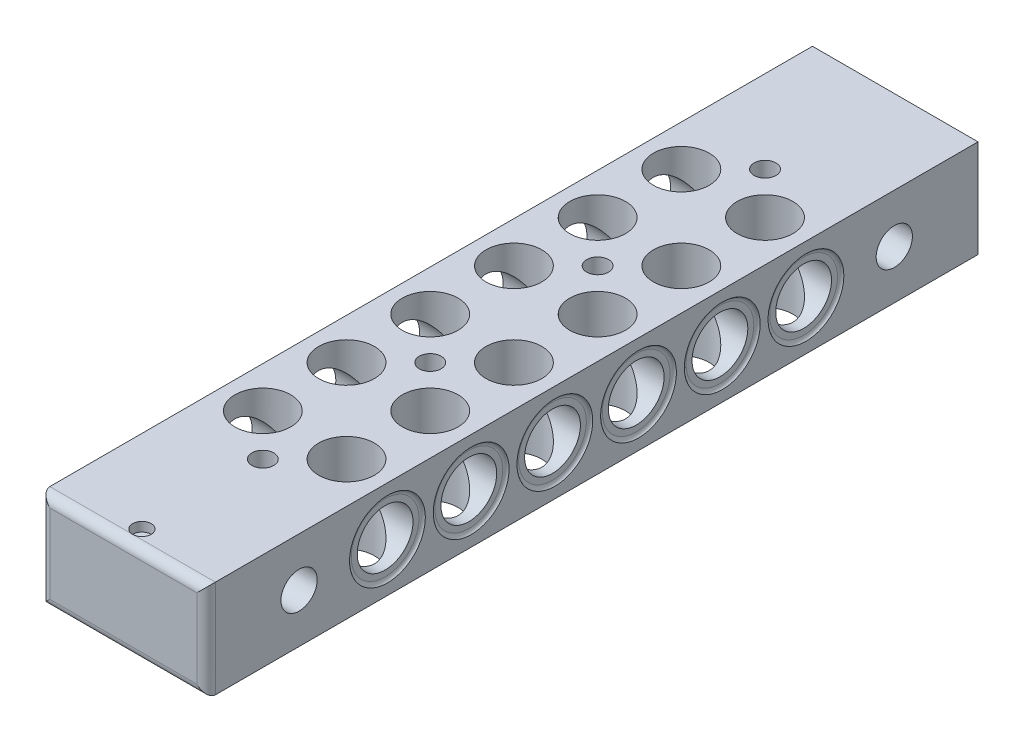
SolidWorks part; units mm, degrees
ref_plane "Front Plane" through (0, 0, 0) normal (0, 0, 1) x (1, 0, 0)
ref_plane "Top Plane" through (0, 0, 0) normal (0, 1, 0) x (1, 0, 0)
ref_plane "Right Plane" through (0, 0, 0) normal (1, 0, 0) x (0, 0, -1)
sketch "Sketch1" plane through (0, 0, 0) normal (0, 1, 0) x (1, 0, 0)
  line L1 (0, -5.775) -> (0, 5.775) construction
  line L3 (-5.775, 0) -> (5.775, 0) construction
  line L4 (0, 41) -> (-8.9, 41)
  line L5 (0, 41) -> (0, -42)
  line L6 (0, -42) -> (-8.9, -42)
  line L7 (-8.9, 41) -> (-8.9, -42)
  line L8 (0, 41) -> (8.9, 41)
  line L9 (0, 41) -> (0, -42)
  line L10 (0, -42) -> (8.9, -42)
  line L11 (8.9, 41) -> (8.9, -42)
  circle A0 centre (-4.5, -22.5) radius 3
  circle A1 centre (4.5, -22.5) radius 3
  circle A2 centre (4.5, -13.5) radius 3
  circle A3 centre (4.5, -4.5) radius 3
  circle A4 centre (4.5, 4.5) radius 3
  circle A5 centre (4.5, 13.5) radius 3
  circle A6 centre (4.5, 22.5) radius 3
  circle A7 centre (-4.5, -13.5) radius 3
  circle A8 centre (-4.5, -4.5) radius 3
  circle A9 centre (-4.5, 4.5) radius 3
  circle A10 centre (-4.5, 13.5) radius 3
  circle A11 centre (-4.5, 22.5) radius 3
  circle A12 centre (0, -27) radius 1.175
  circle A13 centre (0, -9) radius 1.175
  circle A14 centre (0, 9) radius 1.175
  circle A15 centre (0, 27) radius 1.175
  point P6 (0, 0)
  dimension "D4" = 6
  dimension "D5" = 42
  dimension "D7" = 4.5
  dimension "D8" = 2
  dimension "D10" = 9
  dimension "D11" = 2.35
  dimension "D12" = 27
  dimension "D14" = 18
  dimension "D15" = 9
  dimension "D1" = 41
  dimension "D2" = 8.9
  dimension "D3" = 8.9
  dimension "D6" = 22.5
  dimension "D9" = 6
  dimension "D13" = 4
extrude "Boss-Extrude1" add sketch "Sketch1" along normal blind 10.5 contours A15 L5 L4 L7 L6 A12 A13 A14 A11 A10 A9 A8 A7 A0 | A15 L5 A14 A13 A12 L10 L11 L8 A6 A5 A4 A3 A2 A1 region at (-4.496, 0, 0.6591) region at (4.496, 0, 0.6591)
sketch "Sketch3" plane through (0, 10.5, 0) normal (0, 1, 0) x (1, 0, 0)
  line L0 (0, -5.775) -> (0, 5.775) construction
  line L1 (8.9, -42) -> (-8.9, -42) construction
  circle A0 centre (0, -40) radius 1
  dimension "D1" = 2
  dimension "D2" = 2
extrude "Cut-Extrude1" cut sketch "Sketch3" against normal blind 1
fillet "Fillet1" radius 1 4 edges at (-8.9, 5.25, 42) (0, 10.5, 42) (8.9, 5.25, 42) (0, 0, 42)
sketch "Sketch4" plane through (8.9, 0, 0) normal (1, 0, 0) x (0, 0, -1)
  line L1 (9.845, 0) -> (-9.845, 0) construction
  line L2 (0, 5.775) -> (0, -5.775) construction
  circle A1 centre (-22.5, 5.25) radius 3
  circle A2 centre (-22.5, 5.25) radius 4.075
  circle A3 centre (-13.5, 5.25) radius 3
  circle A4 centre (-4.5, 5.25) radius 3
  circle A5 centre (4.5, 5.25) radius 3
  circle A6 centre (13.5, 5.25) radius 3
  circle A7 centre (22.5, 5.25) radius 3
  circle A8 centre (-13.5, 5.25) radius 4.075
  circle A9 centre (-4.5, 5.25) radius 4.075
  circle A10 centre (4.5, 5.25) radius 4.075
  circle A11 centre (13.5, 5.25) radius 4.075
  circle A12 centre (22.5, 5.25) radius 4.075
  circle A14 centre (32, 5.25) radius 1.95
  circle A15 centre (32, 5.25) radius 5.16
  circle A16 centre (-32, 5.25) radius 1.95
  circle A17 centre (-32, 5.25) radius 5.16
  dimension "D1" = 6
  dimension "D2" = 22.5
  dimension "D3" = 5.25
  dimension "D4" = 8.15
  dimension "D5" = 6
  dimension "D7" = 3.9
  dimension "D8" = 32
  dimension "D9" = 10.32
  dimension "D10" = 9
  dimension "D12" = 64
  dimension "D6" = 6
  dimension "D11" = 2
extrude "Cut-Extrude2" cut sketch "Sketch4" against normal up to next contours A16 | A14 region at (8.9, 5.25, -32) region at (8.9, 5.25, 32)
extrude "Cut-Extrude4" cut sketch "Sketch4<3>" against normal up to next contours A1 | A3 | A4 | A5 | A6 | A7 region at (8.9, 5.25, 22.5) region at (8.9, 5.25, 13.5) region at (8.9, 5.25, 4.5) region at (8.9, 5.25, -4.5) region at (8.9, 5.25, -13.5) region at (8.9, 5.25, -22.5)
sketch "Sketch4<3>" plane through (8.9, 0, 0) normal (1, 0, 0) x (0, 0, -1) same geometry as "Sketch4"
extrude "Cut-Extrude5" cut sketch "Sketch4<4>" against normal blind 0.25 contours A8 A3 | A2 A1 | A9 A4 | A10 A5 | A11 A6 | A12 A7 region at (8.9, 5.25, 26.4597) region at (8.9, 5.25, 17.4597) region at (8.9, 5.25, 8.4597) region at (8.9, 5.25, -0.5403) region at (8.9, 5.25, -9.5403) region at (8.9, 5.25, -18.5403)
sketch "Sketch4<4>" plane through (8.9, 0, 0) normal (1, 0, 0) x (0, 0, -1) same geometry as "Sketch4"
fillet "Fillet8" radius 0.5 6 edges at (8.65, 5.25, 18.425) (8.65, 5.25, 9.425) (8.65, 5.25, -26.575) (8.65, 5.25, -17.575) (8.65, 5.25, -8.575) (8.65, 5.25, 0.425)
mirror "Mirror3" about plane through (0, 0, 0) normal (1, 0, 0) of "Fillet8", "Cut-Extrude5", "Cut-Extrude4"
